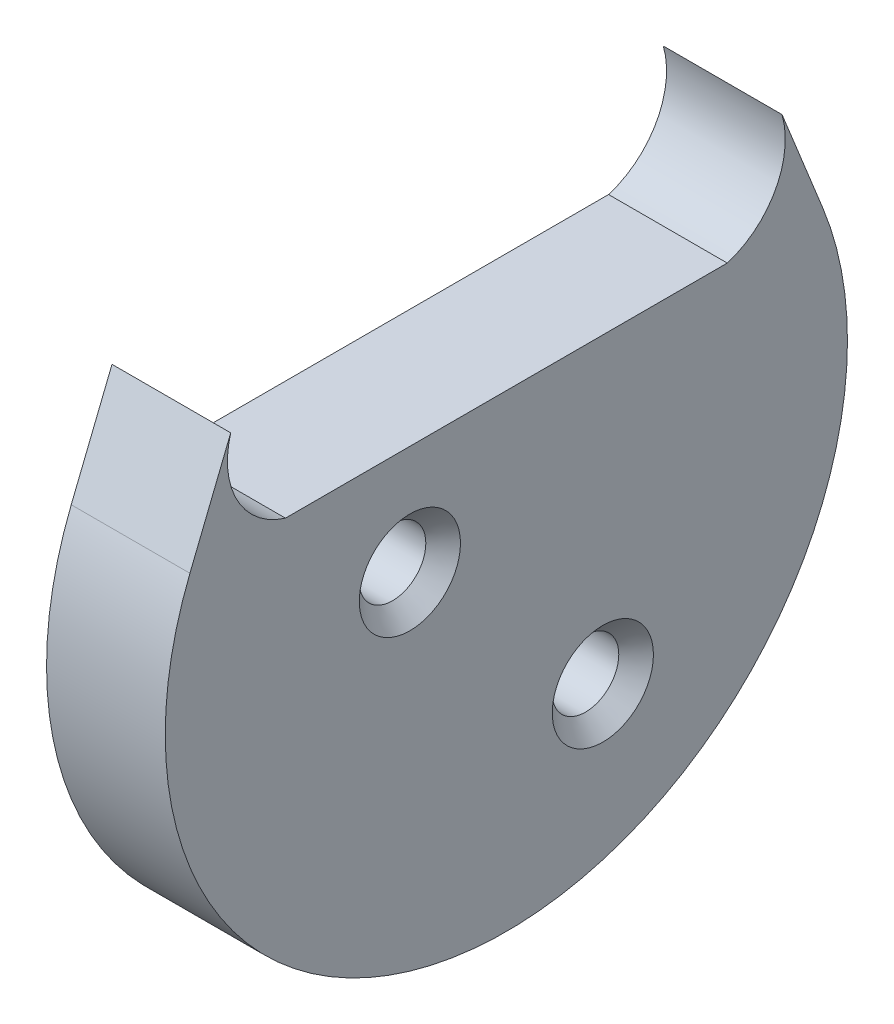
SolidWorks part; units mm, degrees
material "ABS"
ref_plane "Front" through (0, 0, 0) normal (0, 0, 1) x (1, 0, 0)
ref_plane "Top" through (0, 0, 0) normal (0, 1, 0) x (1, 0, 0)
ref_plane "Right" through (0, 0, 0) normal (1, 0, 0) x (0, 0, -1)
sketch "Sketch1" plane through (0, 0, 0) normal (1, 0, 0) x (0, 0, -1)
  line L0 (-11.5955, 4.6684) -> (11.5955, 4.6684)
  line L1 (-11.5955, 4.6684) -> (-10.1016, 8.379)
  line L2 (11.5955, 4.6684) -> (10.1016, 8.379)
  arc A0 (-11.5955, 4.6684) -> (11.5955, 4.6684) centre (0, 0) ccw
  arc A1 (-10.1016, 8.379) -> (-8.0955, 4.6684) centre (-7.2218, 7.5384) ccw
  arc A2 (10.1016, 8.379) -> (8.0955, 4.6684) centre (7.2218, 7.5384) cw
  dimension "D1" = 12.5
  dimension "D4" = 3.5
  dimension "3" = 3
  dimension "D2" = 23.191
  dimension "D3" = 4
  dimension "D5" = 3.5
extrude "Boss-Extrude1" add sketch "Sketch1" along normal mid plane 4.35 contours A1 L1 L0 | L2 A2 L0 | L0 A0 region at (0, 5.6196, 10.2621) region at (0, 5.6196, -10.2621)
sketch "Sketch2" plane through (2.175, 0, 0) normal (1, 0, 0) x (0, 0, -1)
  line L0 (0, 4.6684) -> (0, 0.6684) construction
  line L2 (-3.5355, 0.6684) -> (3.5355, 0.6684) construction
  line L3 (3.5355, 0.6684) -> (-3.5355, -6.4026) construction
  line L4 (-3.5355, 0.6684) -> (3.5355, -6.4026) construction
  line L5 (-8.0955, 4.6684) -> (8.0955, 4.6684) construction
  point P7 (0, 0.6684)
  point P10 (0, -2.8671)
  dimension "D1" = 4
  dimension "D2" = 10
hole_wizard "#2 Clearance Hole2" positions "3DSketch1" profile "Sketch6" hole size "#2" standard "ANSI Inch" end condition through all
sketch3d "3DSketch1"
  point P10 (2.175, 0.6684, 3.5355)
  point P13 (2.175, -6.4026, -3.5355)
sketch "Sketch6" plane through (2.175, 0.6684, 3.5355) normal (0, 1, 0) x (0, 0, -1)
  line L0 (0, 0) -> (0, 4.35)
  line L1 (0, 4.35) -> (1.2192, 4.35)
  line L2 (1.2192, 4.35) -> (1.2192, 0.635)
  line L3 (1.2192, 0.635) -> (1.8542, 0)
  line L5 (1.8542, 0) -> (0, 0)
  line L6 (-1.2192, 0.635) -> (-1.8542, 0) construction
  line L11 (0, -6.35) -> (0, 107.95) construction
  dimension "Thru Hole Dia." = 2.4384
  dimension "Thru Hole Depth" = 4.35
  dimension "Near C'Sink Dia." = 3.7084
  dimension "Near C'Sink Angle" = 90
